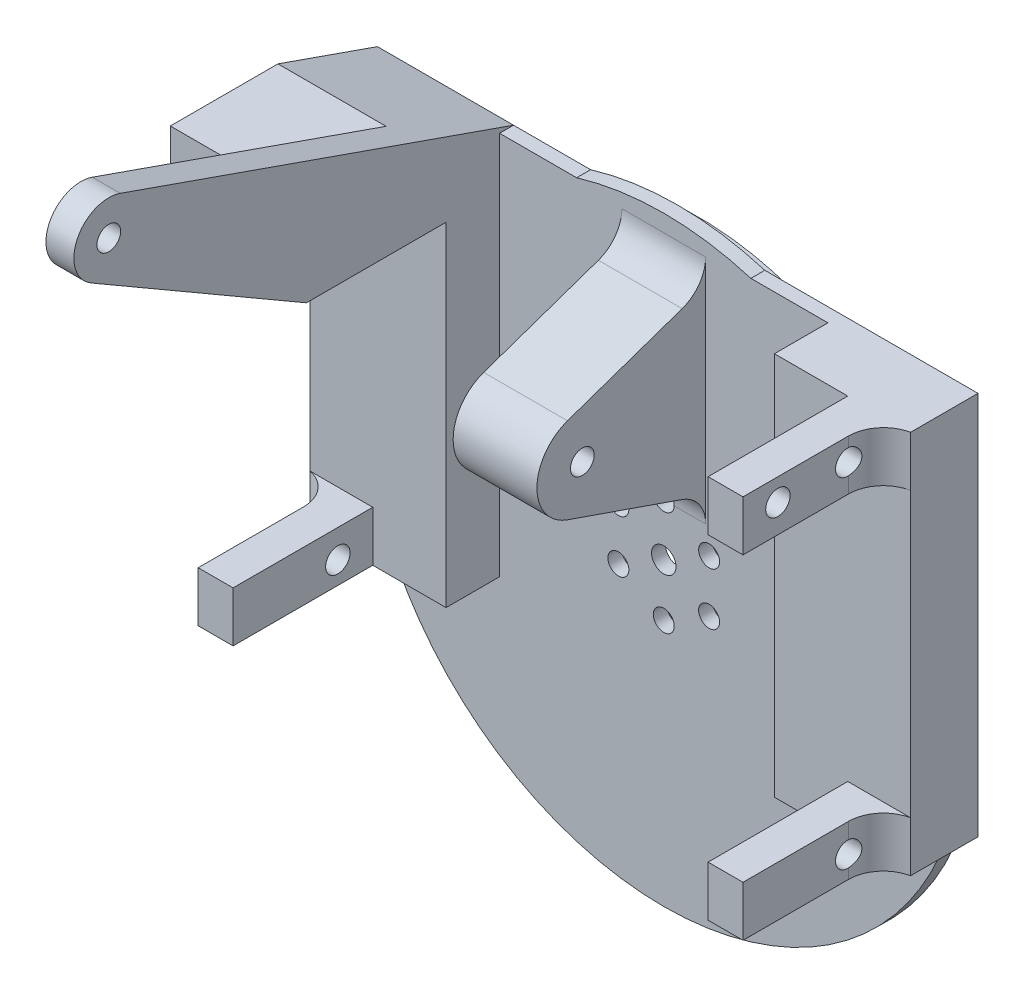
SolidWorks part; units mm, degrees
ref_plane "前视基准面" through (0, 0, 0) normal (0, 0, 1) x (1, 0, 0)
ref_plane "上视基准面" through (0, 0, 0) normal (0, 1, 0) x (1, 0, 0)
ref_plane "右视基准面" through (0, 0, 0) normal (1, 0, 0) x (0, 0, -1)
sketch "草图2" plane through (0, 0, 0) normal (0, 0, 1) x (1, 0, 0)
  line L24 (-3.8438, 6.6576) -> (-10.4181, 9.2102)
  line L25 (-13.1853, 4.4173) -> (-7.6876, 0)
  line L26 (-7.6876, 0) -> (-13.1853, -4.4173)
  line L27 (-10.4181, -9.2102) -> (-3.8438, -6.6576)
  line L28 (-3.8438, -6.6576) -> (-2.7672, -13.6274)
  line L29 (2.7672, -13.6274) -> (3.8438, -6.6576)
  line L30 (3.8438, -6.6576) -> (10.4181, -9.2102)
  line L31 (13.1853, -4.4173) -> (7.6876, 0)
  line L32 (7.6876, 0) -> (13.1853, 4.4173)
  line L33 (10.4181, 9.2102) -> (3.8438, 6.6576)
  line L34 (3.8438, 6.6576) -> (2.7672, 13.6274)
  line L35 (-2.7672, 13.6274) -> (-3.8438, 6.6576)
  line L36 (-3.8438, 6.6576) -> (-10.4181, 9.2102)
  line L37 (-13.1853, 4.4173) -> (-7.6876, 0)
  line L38 (-7.6876, 0) -> (-13.1853, -4.4173)
  line L39 (-10.4181, -9.2102) -> (-3.8438, -6.6576)
  line L40 (-3.8438, -6.6576) -> (-2.7672, -13.6274)
  line L41 (2.7672, -13.6274) -> (3.8438, -6.6576)
  line L42 (3.8438, -6.6576) -> (10.4181, -9.2102)
  line L43 (13.1853, -4.4173) -> (7.6876, 0)
  line L44 (7.6876, 0) -> (13.1853, 4.4173)
  line L45 (10.4181, 9.2102) -> (3.8438, 6.6576)
  line L46 (3.8438, 6.6576) -> (2.7672, 13.6274)
  line L47 (-2.7672, 13.6274) -> (-3.8438, 6.6576)
  circle A0 centre (0, 0) radius 40
  arc A13 (-10.4181, 9.2102) -> (-13.1853, 4.4173) centre (-11.4315, 6.6) ccw
  arc A14 (-13.1853, -4.4173) -> (-10.4181, -9.2102) centre (-11.4315, -6.6) ccw
  arc A15 (-2.7672, -13.6274) -> (2.7672, -13.6274) centre (0, -13.2) ccw
  arc A16 (10.4181, -9.2102) -> (13.1853, -4.4173) centre (11.4315, -6.6) ccw
  arc A17 (13.1853, 4.4173) -> (10.4181, 9.2102) centre (11.4315, 6.6) ccw
  arc A18 (2.7672, 13.6274) -> (-2.7672, 13.6274) centre (0, 13.2) ccw
  arc A19 (-10.4181, 9.2102) -> (-13.1853, 4.4173) centre (-11.4315, 6.6) ccw
  arc A20 (-13.1853, -4.4173) -> (-10.4181, -9.2102) centre (-11.4315, -6.6) ccw
  arc A21 (-2.7672, -13.6274) -> (2.7672, -13.6274) centre (0, -13.2) ccw
  arc A22 (10.4181, -9.2102) -> (13.1853, -4.4173) centre (11.4315, -6.6) ccw
  arc A23 (13.1853, 4.4173) -> (10.4181, 9.2102) centre (11.4315, 6.6) ccw
  arc A24 (2.7672, 13.6274) -> (-2.7672, 13.6274) centre (0, 13.2) ccw
  dimension "D1" = 80
  dimension "D2" = 0.3
extrude "凸台-拉伸1" add sketch "草图2" against normal blind 3
sketch "草图3" plane through (0, 0, 0) normal (0, 0, 1) x (1, 0, 0)
  circle A0 centre (0, 0) radius 43
  circle A1 centre (0, -7.5) radius 1.5
  circle A2 centre (-6.4952, -3.75) radius 1.5
  circle A3 centre (-6.4952, 3.75) radius 1.5
  circle A4 centre (0, 7.5) radius 1.5
  circle A5 centre (6.4952, 3.75) radius 1.5
  circle A6 centre (6.4952, -3.75) radius 1.5
  circle A7 centre (0, 0) radius 1.75
  point P19 (0, 0)
  dimension "D1" = 6
  dimension "D2" = 86
extrude "凸台-拉伸2" add sketch "草图3" along normal blind 2
sketch "草图4" plane through (0, 0, 0) normal (1, 0, 0) x (0, 0, -1)
  line L0 (-21.791, 17.8583) -> (-2, 11)
  line L1 (-2, 11) -> (-2, 37)
  line L3 (-2, 24) -> (-29.0444, 24) construction
  line L4 (0, 24) -> (-119.2624, 24) construction
  line L5 (-21.791, 30.1417) -> (-2, 37)
  circle A0 centre (-19.6627, 24) radius 1.7
  arc A1 (-21.791, 30.1417) -> (-21.791, 17.8583) centre (-19.6627, 24) ccw
  dimension "D1" = 3.4
  dimension "D2" = 13
  dimension "D3" = 13
extrude "凸台-拉伸3" add sketch "草图4" along normal mid plane 12
sketch "草图6" plane through (0, 0, 0) normal (0, 0, -1) x (-1, 0, 0)
  line L1 (23.5106, -13.85) -> (43, -13.85)
  line L2 (23.5106, -13.85) -> (23.5106, 41.15)
  line L3 (23.5106, 41.15) -> (43, 41.15)
  line L4 (43, -13.85) -> (43, 41.15)
  circle A0 centre (0, 0) radius 43 construction
extrude "凸台-拉伸4" add sketch "草图6" against normal up to surface (9.6627 mm away)
sketch "草图7" plane through (0, 0, 9.6627) normal (0, 0, 1) x (1, 0, 0)
  line L1 (-39.0106, 41.15) -> (-34.0106, 41.15)
  line L2 (-39.0106, 41.15) -> (-39.0106, 33.95)
  line L3 (-39.0106, 33.95) -> (-34.0106, 33.95)
  line L4 (-34.0106, 41.15) -> (-34.0106, 33.95)
  line L7 (-34.0106, -13.85) -> (-39.0106, -13.85)
  line L8 (-34.0106, -13.85) -> (-34.0106, -6.65)
  line L9 (-34.0106, -6.65) -> (-39.0106, -6.65)
  line L10 (-39.0106, -13.85) -> (-39.0106, -6.65)
  line L12 (-43, 41.15) -> (-23.5106, 41.15) construction
  line L13 (-34.0106, 41.15) -> (-34.0106, 33.65) construction
  line L14 (-23.5106, -13.85) -> (-43, -13.85) construction
  line L15 (-34.0106, -6.35) -> (-34.0106, -13.85) construction
  dimension "D1" = 5
  dimension "D2" = 5
extrude "凸台-拉伸5" add sketch "草图7" along normal up to surface (20 mm away)
fillet "圆角1" radius 5 2 edges at (-39.0106, -10.25, 9.6627)
sketch "草图8" plane through (-34.0106, 0, 0) normal (1, 0, 0) x (0, 0, -1)
  circle A0 centre (-14.6627, 37.965) radius 1.75
  circle A1 centre (-24.6627, 37.965) radius 1.75
  circle A2 centre (-14.6627, -10.665) radius 1.75
  circle A3 centre (24.6627, -10.665) radius 1.75
extrude "切除-拉伸1" cut sketch "草图8" against normal blind 8
mirror "镜向1" about plane through (0, 0, 0) normal (1, 0, 0) of "切除-拉伸1", "圆角1", "凸台-拉伸5", "凸台-拉伸4"
fillet "圆角2" radius 5 2 edges at (0, 11, 2) (0, 37, 2)
sketch "草图10" plane through (-23.5106, 0, 0) normal (1, 0, 0) x (0, 0, -1)
  line L0 (-56.3132, 60.8587) -> (0, 41.15)
  line L1 (-60.4729, 51.8139) -> (-29.6627, 33.95)
  line L2 (-29.6627, 33.95) -> (0, 33.95)
  line L3 (0, -13.85) -> (0, 41.15) construction
  line L4 (0, 33.95) -> (0, 41.15)
  circle A0 centre (-57.9649, 56.1394) radius 1.7
  circle A1 centre (-57.9649, 56.1394) radius 5
  line M5 (0, 41.15) -> (-9.6627, 41.15)
  line M6 (-9.6627, 41.15) -> (-9.6627, -13.85)
extrude "凸台-拉伸6" add sketch "草图10" against normal blind 4 contours A1 L1 L2 L0 M6 M5 | A1 A0 region at (-23.5106, 44.9715, 31.6624) region at (-23.5106, 58.9508, 54.0024)
sketch "草图11" plane through (-43, 0, 0) normal (-1, 0, 0) x (0, 0, 1)
  line L0 (0, 41.15) -> (29.6627, 41.15)
  line L1 (29.6627, 41.15) -> (29.6627, 46.1381)
  line L4 (29.6627, 46.1381) -> (14.2524, 46.1381)
  line L5 (56.3132, 60.8587) -> (0, 41.15) construction
  line L6 (14.2524, 46.1381) -> (0, 41.15)
extrude "凸台-拉伸7" add sketch "草图11" against normal up to surface (15.4894 mm away) up to face at (-27.5106, 44.1275, 28.3148)
sketch "草图13" plane through (0, 0, 0) normal (0, 0, -1) x (-1, 0, 0)
  line L0 (23.5106, 41.15) -> (23.5106, 36.0035) construction
  line L1 (23.5106, 41.15) -> (-25.4678, 41.15)
  line L2 (23.5106, 41.15) -> (23.5106, 35.1971)
  line L3 (23.5106, 35.1971) -> (-25.4678, 35.1971)
  line L4 (-25.4678, 41.15) -> (-25.4678, 35.1971)
extrude "凸台-拉伸8" add sketch "草图13" against normal up to surface (2 mm away) up to face at (7.9952, 3.75, 2)
